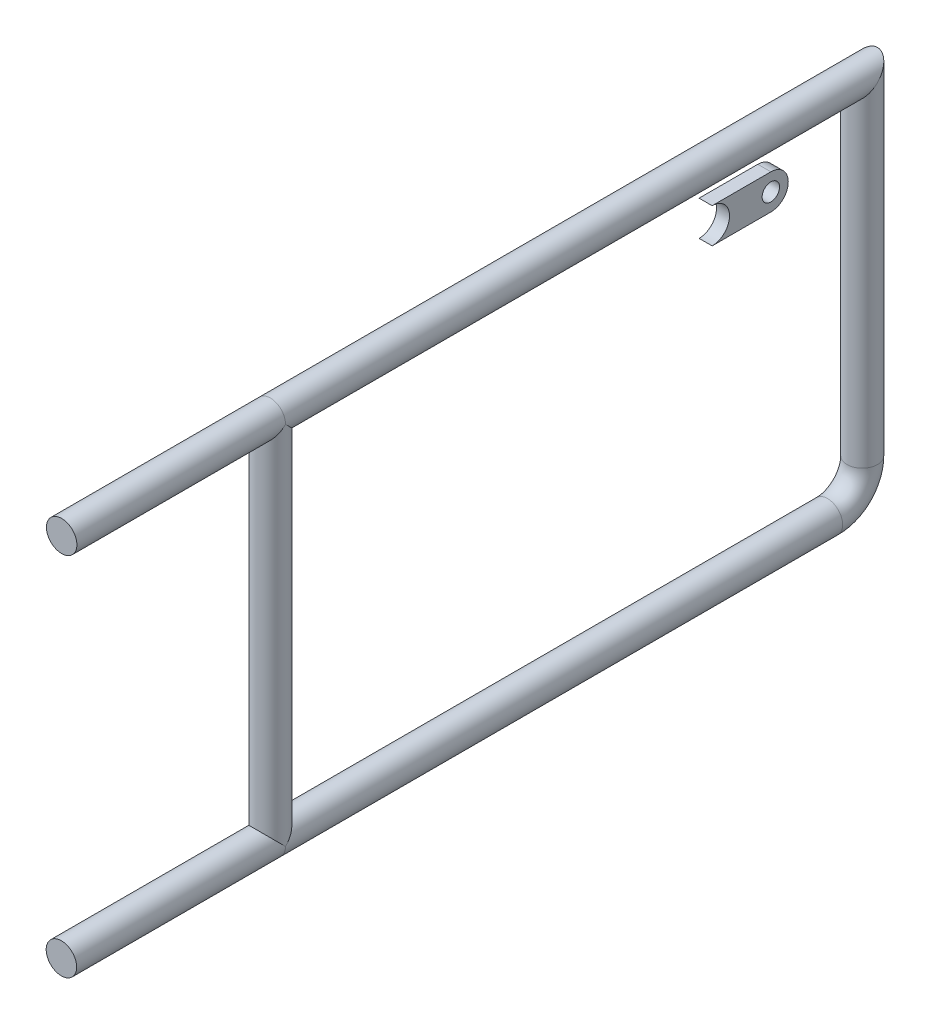
SolidWorks part; units mm, degrees
note: The reader was unsure of these and kept them because the rebuilt part matched: shared geometry of "Sketch3<8>", "Sketch1<23>".
ref_plane "Front Plane" through (0, 0, 0) normal (0, 0, 1) x (1, 0, 0)
ref_plane "Top Plane" through (0, 0, 0) normal (0, 1, 0) x (1, 0, 0)
ref_plane "Right Plane" through (0, 0, 0) normal (1, 0, 0) x (0, 0, -1)
sketch "Sketch1" plane through (0, 0, 0) normal (1, 0, 0) x (0, 0, -1)
  line L0 (126.1633, -30.1592) -> (152.2128, -152.4)
  line L2 (152.2128, -431.8) -> (584.0128, -431.8)
  line L4 (584.0128, -673.1) -> (584.0128, -431.8)
  line L5 (152.2128, -431.8) -> (0, -431.8)
  line L6 (558.6128, -698.5) -> (152.2128, -698.5)
  line L7 (88.9, 0) -> (0, 0)
  line L8 (152.2128, -152.4) -> (431.6128, -152.4)
  line L10 (457.0128, -177.8) -> (457.0128, -273.05)
  line L16 (457.0128, -273.05) -> (558.6128, -273.05)
  line L17 (584.0128, -298.45) -> (584.0128, -431.8)
  line L18 (-0.1872, -698.5) -> (152.2128, -698.5)
  line L19 (152.2128, -698.5) -> (152.2128, -431.8)
  line L20 (152.2128, -152.4) -> (152.2128, -431.8)
  arc A0 (88.9, 0) -> (126.1633, -30.1592) centre (88.9, -38.1) cw
  arc A1 (584.0128, -673.1) -> (558.6128, -698.5) centre (558.6128, -673.1) cw
  arc A2 (584.0128, -298.45) -> (558.6128, -273.05) centre (558.6128, -298.45) ccw
  arc A3 (431.6128, -152.4) -> (457.0128, -177.8) centre (431.6128, -177.8) cw
  point P5 (584.0128, -698.5)
  point P24 (584.0128, -273.05)
  point P30 (457.0128, -152.4)
  dimension "D2" = 38.1
  dimension "D11" = 25.4
  dimension "D9" = 25.4
  dimension "D1" = 88.9
  dimension "D3" = 120.65
  dimension "D4" = 431.8
  dimension "D5" = 431.8
  dimension "D6" = 279.4
  dimension "D7" = 152.4
  dimension "D8" = 546.1
  dimension "D10" = 127
  dimension "D17" = 124.9856
sketch "Sketch3" plane through (0, 0, 0) normal (0, 0, 1) x (1, 0, 0)
  circle A0 centre (0, -698.5) radius 11.1125
  dimension "D1" = 22.225
sweep "Sweep1" add profiles "Sketch3" path "Sketch1"
sweep "Sweep2" add profiles "Sketch3<8>" path "Sketch1<23>"
sketch "Sketch3<8>" plane through (0, 0, 0) normal (0, 0, 1) x (1, 0, 0) same geometry as "Sketch3"
sketch "Sketch1<23>" plane through (0, 0, 0) normal (1, 0, 0) x (0, 0, -1) same geometry as "Sketch1"
sketch "Sketch10" plane through (0, 0, 0) normal (1, 0, 0) x (0, 0, -1)
  line L1 (152.4, -914.4) -> (-272.7134, -914.4)
  line L2 (152.2128, -698.5) -> (152.2128, -431.8) construction
  circle A0 centre (152.2128, -609.6) radius 304.8
  dimension "D1" = 609.6
  dimension "D2" = 88.9
sketch "Sketch11" plane through (0, 0, 0) normal (1, 0, 0) x (0, 0, -1)
  line L0 (584.0128, -647.7) -> (152.2128, -647.7)
  line L1 (584.0128, -673.1) -> (584.0128, -431.8) construction
  line L2 (152.2128, -698.5) -> (152.2128, -431.8) construction
  line L3 (152.2128, -647.7) -> (152.2128, -698.5)
  line L4 (152.2128, -698.5) -> (558.6128, -698.5)
  line L5 (584.0128, -673.1) -> (584.0128, -647.7)
  line L6 (584.0128, -431.8) -> (584.0128, -482.6)
  line L7 (584.0128, -482.6) -> (152.2128, -482.6)
  line L8 (152.2128, -482.6) -> (152.2128, -431.8)
  line L9 (152.2128, -431.8) -> (584.0128, -431.8)
  line L10 (380.8128, -463.55) -> (177.6128, -666.75) construction
  line L11 (389.793, -472.5303) -> (186.593, -675.7303)
  line L12 (371.8325, -454.5697) -> (168.6325, -657.7697)
  line L13 (380.8128, -666.75) -> (177.6128, -463.55) construction
  line L14 (371.8325, -675.7303) -> (168.6325, -472.5303)
  line L15 (389.793, -657.7697) -> (186.593, -454.5697)
  line L16 (380.8128, -463.55) -> (507.8128, -463.55) construction
  line L17 (380.8128, -450.85) -> (507.8128, -450.85)
  line L18 (380.8128, -476.25) -> (507.8128, -476.25)
  line L19 (380.8128, -666.75) -> (507.8128, -666.75) construction
  line L20 (380.8128, -654.05) -> (507.8128, -654.05)
  line L21 (380.8128, -679.45) -> (507.8128, -679.45)
  line L22 (177.6128, -463.55) -> (177.6128, -666.75) construction
  line L23 (177.6128, -565.15) -> (446.4211, -666.75) construction
  line L24 (177.6128, -666.75) -> (446.4211, -565.15) construction
  line L25 (177.6128, -532.9233) -> (431.9175, -666.75) construction
  line L26 (431.9175, -666.75) -> (431.9175, -532.9233) construction
  line L27 (431.9175, -532.9233) -> (177.6128, -666.75) construction
  line L28 (464.982, -666.75) -> (464.982, -463.55) construction
  arc A0 (584.0128, -673.1) -> (558.6128, -698.5) centre (558.6128, -673.1) cw
  circle A1 centre (177.6128, -463.55) radius 6.35
  circle A2 centre (177.6128, -666.75) radius 6.35
  circle A3 centre (279.2128, -565.15) radius 6.35
  arc A4 (380.8128, -450.85) -> (380.8128, -476.25) centre (380.8128, -463.55) ccw
  arc A5 (389.793, -472.5303) -> (371.8325, -454.5697) centre (380.8128, -463.55) ccw
  arc A6 (168.6325, -657.7697) -> (186.593, -675.7303) centre (177.6128, -666.75) ccw
  arc A7 (371.8325, -675.7303) -> (389.793, -657.7697) centre (380.8128, -666.75) ccw
  arc A8 (186.593, -454.5697) -> (168.6325, -472.5303) centre (177.6128, -463.55) ccw
  arc A9 (507.8128, -476.25) -> (507.8128, -450.85) centre (507.8128, -463.55) ccw
  arc A10 (380.8128, -654.05) -> (380.8128, -679.45) centre (380.8128, -666.75) ccw
  arc A11 (507.8128, -679.45) -> (507.8128, -654.05) centre (507.8128, -666.75) ccw
  arc A12 (380.8128, -463.55) -> (464.982, -666.75) centre (177.6064, -666.7541) cw
  circle A13 centre (380.8128, -463.55) radius 6.35
  circle A14 centre (380.8128, -666.75) radius 6.35
  circle A15 centre (507.8128, -463.55) radius 6.35
  arc A16 (464.982, -476.25) -> (464.982, -450.85) centre (464.982, -463.55) ccw
  point P12 (584.0128, -698.5)
  point P27 (279.2128, -565.15)
  point P32 (279.2128, -565.15)
  point P39 (444.3128, -463.55)
  point P44 (444.3128, -666.75)
  dimension "D1" = 25.4
  dimension "D4" = 12.7
  dimension "D5" = 12.7
  dimension "D8" = 12.7
  dimension "D12" = 287.3756
  dimension "D13" = 12.7
  dimension "D2" = 50.8
  dimension "D3" = 50.8
  dimension "D6" = 19.05
  dimension "D7" = 19.05
  dimension "D9" = 90
  dimension "D10" = 25.4
  dimension "D11" = 76.2
extrude "Boss-Extrude1" add sketch "Sketch11" along normal blind 9.525 separate body contours A16 L18 A9 L17 A15 | A2 | A3 | A13 | L11 A6 L12 A5
